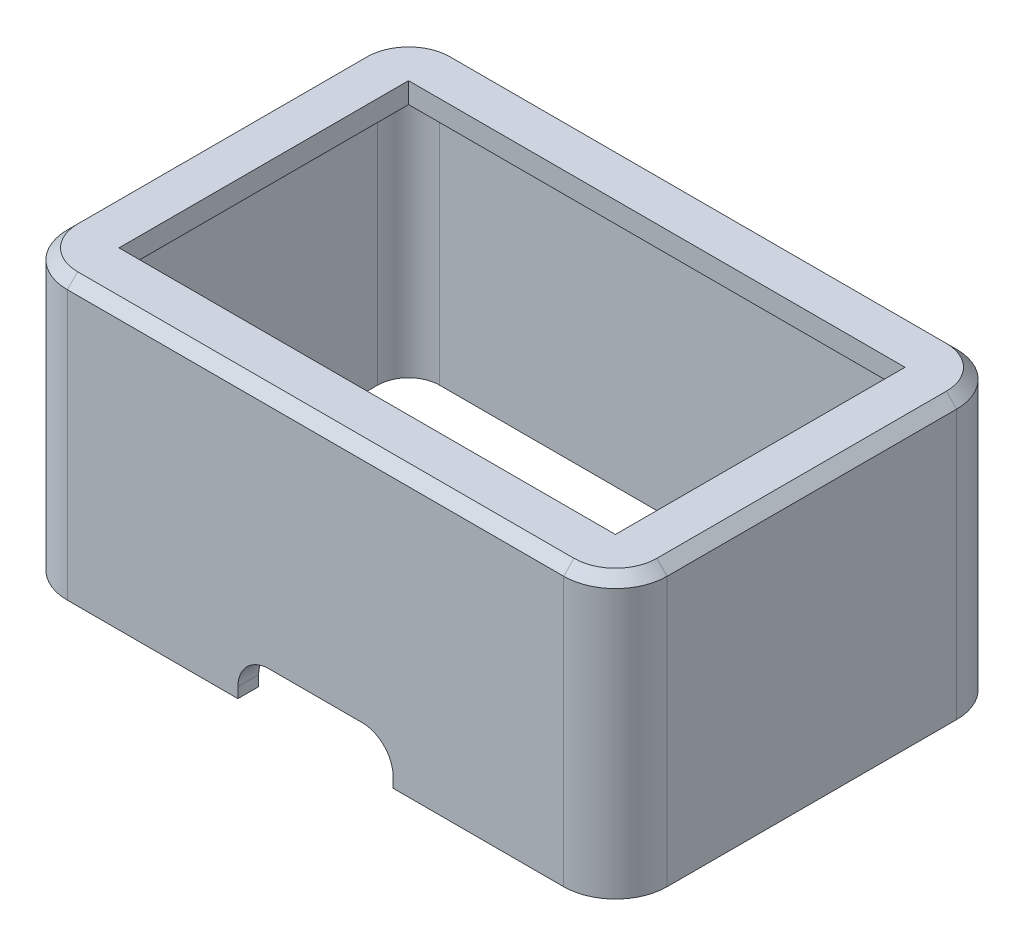
SolidWorks part; units mm, degrees
ref_plane "Front Plane" through (0, 0, 0) normal (0, 0, 1) x (1, 0, 0)
ref_plane "Top Plane" through (0, 0, 0) normal (0, 1, 0) x (1, 0, 0)
ref_plane "Right Plane" through (0, 0, 0) normal (1, 0, 0) x (0, 0, -1)
sketch "Sketch2" plane through (0, 0, 0) normal (0, 1, 0) x (1, 0, 0)
  line L1 (-29, 19) -> (29, 19)
  line L2 (-29, 19) -> (-29, -19)
  line L3 (-29, -19) -> (29, -19)
  line L4 (29, 19) -> (29, -19)
  line L5 (-29, 19) -> (29, -19) construction
  line L6 (-29, -19) -> (29, 19) construction
  line L7 (-24, 14) -> (24, 14)
  line L8 (-24, 14) -> (-24, -14)
  line L9 (-24, -14) -> (24, -14)
  line L10 (24, 14) -> (24, -14)
  line L11 (-24, 14) -> (24, -14) construction
  line L12 (-24, -14) -> (24, 14) construction
  point P0 (0, 0)
  point P5 (0, 0)
  point P11 (32.5665, 30.5)
  dimension "D1" = 5
  dimension "D2" = 48
  dimension "D3" = 28
  dimension "D4" = 5
extrude "Boss-Extrude1" add sketch "Sketch2" along normal blind 2
sketch "Sketch3" plane through (0, 0, 0) normal (0, -1, 0) x (1, 0, 0)
  line L8 (27, -17) -> (27, 17)
  line L9 (27, 17) -> (-27, 17)
  line L10 (-27, 17) -> (-27, -17)
  line L11 (-27, -17) -> (27, -17)
  line L12 (27, -17) -> (27, 17)
  line L13 (27, 17) -> (-27, 17)
  line L14 (-27, 17) -> (-27, -17)
  line L15 (-27, -17) -> (27, -17)
  line L16 (29, -19) -> (29, 19)
  line L17 (29, 19) -> (-29, 19)
  line L18 (-29, 19) -> (-29, -19)
  line L19 (-29, -19) -> (29, -19)
  line L20 (29, -19) -> (29, 19)
  line L21 (29, 19) -> (-29, 19)
  line L22 (-29, 19) -> (-29, -19)
  line L23 (-29, -19) -> (29, -19)
  dimension "D1" = 2
  dimension "D2" = 0
extrude "Boss-Extrude2" add sketch "Sketch3" along normal blind 25
fillet "Fillet1" radius 3 4 edges at (-27, -12.5, 17) (27, -12.5, 17) (-27, -12.5, -17) (27, -12.5, -17)
fillet "Fillet2" radius 5 4 edges at (-29, -11.5, 19) (-29, -11.5, -19) (29, -11.5, -19) (29, -11.5, 19)
sketch "Sketch4" plane through (0, 0, 19) normal (0, 0, 1) x (1, 0, 0)
  line L0 (-7.5, -25) -> (-7.5, -21)
  line L1 (24, -25) -> (-24, -25) construction
  line L2 (-7.5, -21) -> (7.5, -21)
  line L3 (7.5, -21) -> (7.5, -25)
  line L4 (7.5, -25) -> (-7.5, -25)
  point P4 (0, -21)
  dimension "D1" = 4
  dimension "D2" = 15
extrude "Cut-Extrude1" cut sketch "Sketch4" against normal up to surface (2 mm away) up to face at (0, -12.5, 17)
fillet "Fillet3" radius 3 2 edges at (7.5, -21, 18) (-7.5, -21, 18)
chamfer "Chamfer1" distance 1 angle 45 8 edges at (-27.5355, 2, -17.5355) (-29, 2, 0) (0, 2, -19) (-27.5355, 2, 17.5355) (27.5355, 2, -17.5355) (0, 2, 19) (29, 2, 0) (27.5355, 2, 17.5355)
sketch "Sketch6" plane through (0, -25, 0) normal (0, -1, 0) x (1, 0, 0)
  line L0 (-29, 14) -> (-29, -14) construction
  line L1 (-29, 4) -> (-14, 4)
  line L2 (-29, 4) -> (-29, -4)
  line L3 (-29, -4) -> (-14, -4)
  line L4 (-14, 4) -> (-14, -4)
  line L5 (-14, 0) -> (-27, 0) construction
  line L6 (-27, 14) -> (-27, -14) construction
  line L7 (-24, -14) -> (-24, 14) construction
  circle A0 centre (-19, 0) radius 1.75
  point P6 (-29, 0)
  dimension "D3" = 5
  dimension "D4" = 3.5
  dimension "D1" = 15
  dimension "D2" = 8
extrude "Boss-Extrude3" add sketch "Sketch6" against normal blind 2.5
mirror "Mirror1" about plane through (0, 0, 0) normal (1, 0, 0) of "Boss-Extrude3"
fillet "Fillet4" radius 3 8 edges at (-14, -23.75, -4) (-27, -23.75, -4) (-27, -23.75, 4) (-14, -23.75, 4) (27, -23.75, -4) (14, -23.75, -4) (14, -23.75, 4) (27, -23.75, 4)
